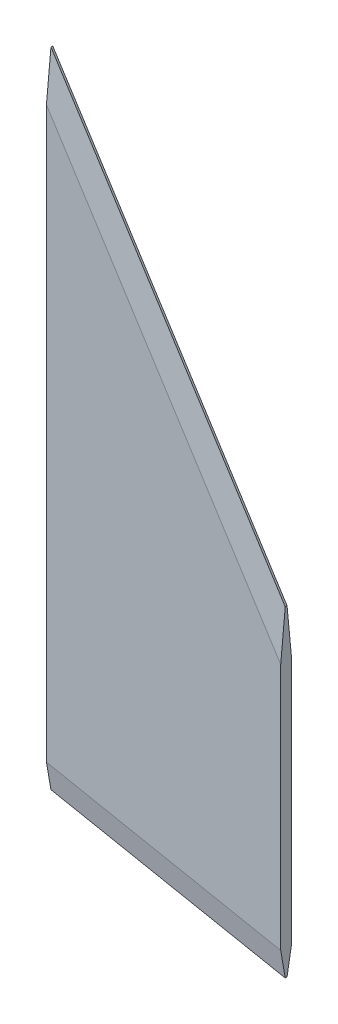
SolidWorks part; units mm, degrees
material "Hexcel AS4C (3000 Filaments)"
ref_plane "Front Plane" through (0, 0, 0) normal (0, 0, 1) x (1, 0, 0)
ref_plane "Top Plane" through (0, 0, 0) normal (0, 1, 0) x (1, 0, 0)
ref_plane "Right Plane" through (0, 0, 0) normal (1, 0, 0) x (0, 0, -1)
sketch "Sketch1" plane through (0, 0, 0) normal (0, 0, 1) x (1, 0, 0)
  line L0 (-60.9816, 77.1065) -> (-60.9816, -100.6935)
  line L1 (-60.9816, -100.6935) -> (3.7884, -113.3935)
  line L2 (3.7884, -113.3935) -> (3.7884, -24.4935)
  line L3 (3.7884, -24.4935) -> (-60.9816, 77.1065)
extrude "Boss-Extrude1" add sketch "Sketch1" along normal mid plane 3
chamfer "Chamfer1" distance 1.25 angle 80 4 edges at (-28.5966, -107.0435, -1.5) (-28.5966, -107.0435, 1.5) (-28.5966, 26.3065, -1.5) (-28.5966, 26.3065, 1.5) first distance on face at (-28.5966, -107.0435, 0) first distance on face at (-28.5966, 26.3065, 0)
